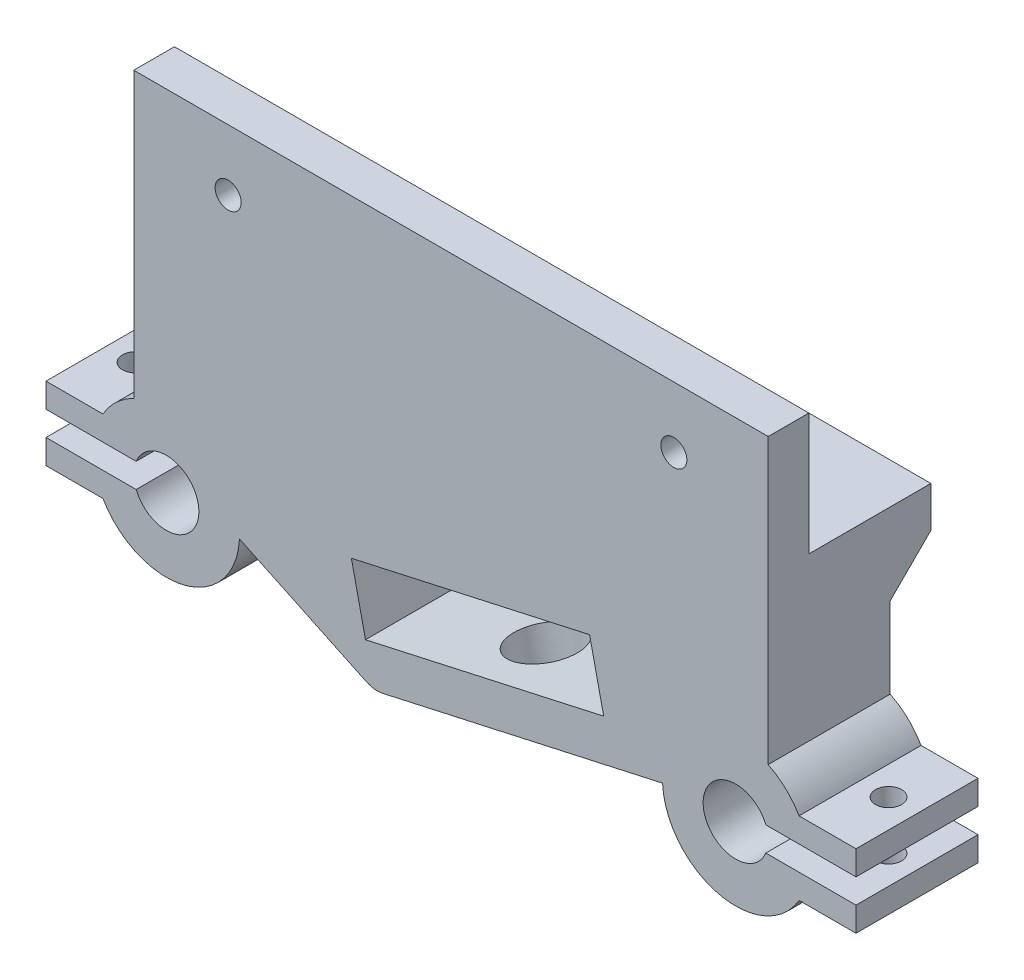
SolidWorks part; units mm, degrees
ref_plane "Front Plane" through (0, 0, 0) normal (0, 0, 1) x (1, 0, 0)
ref_plane "Top Plane" through (0, 0, 0) normal (0, 1, 0) x (1, 0, 0)
ref_plane "Right Plane" through (0, 0, 0) normal (1, 0, 0) x (0, 0, -1)
sketch "Sketch1" plane through (0, 0, 0) normal (0, 0, 1) x (1, 0, 0)
  line L0 (0, -1000) -> (0, 49000) construction
  line L1 (-39, 28) -> (39, 28)
  line L2 (39, 28) -> (39, 8.0623)
  line L3 (36.951, -8.786) -> (-23.8235, -22.2816)
  line L4 (-39, 28) -> (-39, 8.0623)
  line L6 (-34, 23) -> (34, 23)
  line L7 (34, 23) -> (34, 8.9443)
  line L9 (-13.0714, 45.025) -> (10825.8602, -48765.5982) construction
  line L10 (-1035, 0) -> (48965, 0) construction
  line L11 (-34, 23) -> (-34, 8.9443)
  line L12 (-22.3817, -16.8397) -> (-31.7139, -8.3786)
  line L13 (-23.8235, -22.2816) -> (-41.0451, -6.6675)
  line L14 (27.9966, -5.6526) -> (-22.3817, -16.8397)
  line L15 (-49.7942, 4.5) -> (-42.7942, 4.5)
  line L16 (-49.7942, 4.5) -> (-49.7942, 1.5)
  line L17 (-49.7942, 1.5) -> (-38.7081, 1.5)
  line L18 (42.7942, 4.5) -> (49.7942, 4.5)
  line L19 (-49.7942, -1.5) -> (-38.7081, -1.5)
  line L20 (-49.7942, -1.5) -> (-49.7942, -4.5)
  line L21 (-49.7942, -4.5) -> (-42.7942, -4.5)
  line L23 (38.7081, 1.5) -> (49.7942, 1.5)
  line L24 (49.7942, 4.5) -> (49.7942, 1.5)
  line L25 (38.7081, -1.5) -> (49.7942, -1.5)
  line L27 (42.7942, -4.5) -> (49.7942, -4.5)
  line L28 (49.7942, -1.5) -> (49.7942, -4.5)
  arc A0 (-38.7081, -1.5) -> (-38.7081, 1.5) centre (-35, 0) ccw
  arc A1 (38.7081, 1.5) -> (38.7081, -1.5) centre (35, 0) ccw
  arc A2 (34, 8.9443) -> (27.9966, -5.6526) centre (35, 0) ccw
  arc A3 (-39, 8.0623) -> (-42.7942, 4.5) centre (-35, 0) ccw
  arc A4 (-42.7942, -4.5) -> (-41.0451, -6.6675) centre (-35, 0) ccw
  arc A5 (-31.7139, -8.3786) -> (-34, 8.9443) centre (-35, 0) ccw
  arc A6 (36.951, -8.786) -> (42.7942, -4.5) centre (35, 0) ccw
  arc A8 (42.7942, 4.5) -> (39, 8.0623) centre (35, 0) ccw
  dimension "D1" = 8
  dimension "D2" = 70
  dimension "D4" = 18
  dimension "D5" = 19
  dimension "D14" = 9
  dimension "D3" = 102.52
  dimension "D6" = 5
  dimension "D7" = 5
  dimension "D8" = 3
  dimension "D9" = 3
  dimension "D10" = 22.5
  dimension "D11" = 5
  dimension "D12" = 5
  dimension "D13" = 3
  dimension "D15" = 7
  dimension "D16" = 3
  dimension "D17" = 7
  dimension "D18" = 5
  dimension "D19" = 90
  dimension "D20" = 3
sketch "Sketch2" plane through (0, 0, 0) normal (0, 0, 1) x (1, 0, 0)
  line L0 (-39, 28) -> (39, 28)
  line L1 (39, 28) -> (39, 8.0623)
  line L2 (-39, 28) -> (-39, 8.0623)
  line L3 (-42.7942, 4.5) -> (-49.7942, 4.5)
  line L4 (-49.7942, 4.5) -> (-49.7942, 1.5)
  line L5 (-49.7942, 1.5) -> (-38.7081, 1.5)
  line L6 (-38.7081, -1.5) -> (-49.7942, -1.5)
  line L7 (-49.7942, -1.5) -> (-49.7942, -4.5)
  line L8 (-49.7942, -4.5) -> (-42.7942, -4.5)
  line L10 (42.7942, 4.5) -> (49.7942, 4.5)
  line L11 (49.7942, 4.5) -> (49.7942, 1.5)
  line L12 (49.7942, 1.5) -> (38.7081, 1.5)
  line L13 (38.7081, -1.5) -> (49.7942, -1.5)
  line L14 (49.7942, -1.5) -> (49.7942, -4.5)
  line L15 (49.7942, -4.5) -> (42.7942, -4.5)
  line L17 (26.0093, -0.4085) -> (-9.4297, -8.2781)
  line L18 (-9.4297, -8.2781) -> (-26.0093, -0.4085)
  line L19 (27.9966, -5.6526) -> (-22.3817, -16.8397) construction
  line L20 (-43369.1498, 195289.1042) -> (54181.9386, -244009.6774) construction
  line L21 (-9.2108, 4.575) -> (14.2185, 9.7777) construction
  line L22 (-9.2108, 4.575) -> (-7.6933, -2.2586) construction
  line L23 (-7.6933, -2.2586) -> (15.736, 2.9441) construction
  line L24 (14.2185, 9.7777) -> (15.736, 2.9441) construction
  line L25 (-3.2618, 33.1405) -> (10835.7579, -48777.8793) construction
  line L27 (-10.5136, -3.397) -> (-12.2478, 4.4127)
  line L28 (-12.2478, 4.4127) -> (17.0388, 10.9161)
  line L29 (17.0388, 10.9161) -> (18.773, 3.1064)
  line L30 (18.773, 3.1064) -> (-10.5136, -3.397)
  line L32 (17.0388, 10.9161) -> (13.2451, 28) construction
  line L33 (-10.5136, -3.397) -> (-9.4297, -8.2781) construction
  arc A0 (-39, 8.0623) -> (-42.7942, 4.5) centre (-35, 0) ccw
  arc A1 (-39, 8.0623) -> (-42.7942, 4.5) centre (-35, 0) ccw construction
  arc A2 (39, 8.0623) -> (42.7942, 4.5) centre (35, 0) cw
  arc A3 (42.7942, 4.5) -> (39, 8.0623) centre (35, 0) ccw construction
  arc A4 (42.7942, -4.5) -> (26.0093, -0.4085) centre (35, 0) cw
  arc A5 (-42.7942, -4.5) -> (-26.0093, -0.4085) centre (-35, 0) ccw
  arc A6 (-38.7081, 1.5) -> (-38.7081, -1.5) centre (-35, 0) cw
  arc A7 (-38.7081, -1.5) -> (-38.7081, 1.5) centre (-35, 0) ccw construction
  arc A8 (38.7081, 1.5) -> (38.7081, -1.5) centre (35, 0) ccw
  arc A9 (38.7081, 1.5) -> (38.7081, -1.5) centre (35, 0) ccw construction
  dimension "D1" = 24
  dimension "D2" = 5
  dimension "D3" = 7
  dimension "D4" = 30
  dimension "D5" = 8
  dimension "D6" = 0.5
  dimension "D7" = 17.5
  dimension "D8" = 5
extrude "Boss-Extrude1" add sketch "Sketch2" against normal blind 15
sketch "Sketch3" plane through (0, 0, -15) normal (0, 0, -1) x (-1, 0, 0)
  line L0 (-34, 8.9443) -> (-34, 23)
  line L1 (-34, 23) -> (34, 23)
  line L2 (34, 23) -> (34, 8.9443)
  line L3 (-27.5547, 5.0565) -> (10.5136, -3.397)
  line L4 (10.5136, -3.397) -> (-18.773, 3.1064) construction
  line L5 (10.5136, -3.397) -> (12.2478, 4.4127)
  line L6 (12.2478, 4.4127) -> (27.156, 4.4127)
  arc A0 (-27.9966, -5.6526) -> (-34, 8.9443) centre (-35, 0) ccw construction
  arc A1 (34, 8.9443) -> (31.7139, -8.3786) centre (35, 0) ccw construction
  arc A2 (34, 8.9443) -> (27.156, 4.4127) centre (35, 0) ccw
  arc A3 (-34, 8.9443) -> (-27.5547, 5.0565) centre (-35, 0) cw
extrude "Cut-Extrude1" cut sketch "Sketch3" against normal blind 13
sketch "Sketch4" plane through (0, 0, -2) normal (0, 0, -1) x (-1, 0, 0)
  line L0 (-8.2528, 8.9651) -> (-6.5185, 16.7749)
  line L1 (12.2478, 4.4127) -> (-17.0388, 10.9161) construction
  line L2 (5.1961, 14.1735) -> (3.4619, 6.3638)
  line L3 (-6.5185, 16.7749) -> (5.1961, 14.1735)
  line L4 (-8.2528, 8.9651) -> (3.4619, 6.3638)
  line L5 (-3.8346, 1.1835) -> (10835.185, 48812.2033) construction
  line L6 (43369.1498, 195289.1042) -> (-54181.9386, -244009.6774) construction
  line L7 (-17.0388, 10.9161) -> (-18.773, 3.1064) construction
  line L8 (12.2478, 4.4127) -> (10.5136, -3.397) construction
  dimension "D1" = 12
  dimension "D2" = 8
extrude "Boss-Extrude2" add sketch "Sketch4" along normal blind 13
sketch "Sketch5" plane through (1.3087, -5.8935, 0) normal (0.2168, -0.9762, 0) x (0.9762, 0.2168, 0)
  line L0 (-1011, -7.5) -> (48989, -7.5) construction
  line L1 (-11, -15) -> (-11, 0) construction
  line L2 (4, -1015) -> (4, 48985) construction
  line L4 (10, -15) -> (10, -2) construction
  line L5 (-2, -15) -> (-2, -2) construction
  circle A0 centre (4, -7.5) radius 4
  point P7 (-11, -7.5)
  dimension "D1" = 8
extrude "Cut-Extrude2" cut sketch "Sketch5" against normal offset from surface (18 mm away) 5 up to face at (2.3955, 7.6644, -4.75) offset beyond the face yes
sketch "Sketch6" plane through (0, 28, 0) normal (0, 1, 0) x (1, 0, 0)
  line L0 (39, 15) -> (39, 0) construction
  line L1 (-39, 0) -> (39, 0)
  line L2 (-39, 0) -> (-39, 5)
  line L3 (-39, 5) -> (39, 5)
  line L4 (39, 0) -> (39, 5)
  dimension "D1" = 5
extrude "Boss-Extrude3" add sketch "Sketch6" along normal blind 15
sketch "Sketch7" plane through (0, 0, -15) normal (0, 0, -1) x (-1, 0, 0)
  line L0 (-39, 8.0623) -> (-39, 28) construction
  line L1 (39, 28) -> (-39, 28)
  line L2 (39, 28) -> (39, 23)
  line L3 (39, 23) -> (-39, 23)
  line L4 (-39, 28) -> (-39, 23)
  line L5 (34, 23) -> (-34, 23) construction
extrude "Boss-Extrude4" add sketch "Sketch7" along normal blind 5
sketch "Sketch8" plane through (0, 0, -5) normal (0, 0, -1) x (-1, 0, 0)
  line L0 (-961, 35.5) -> (49039, 35.5) construction
  line L1 (39, 43) -> (39, 28) construction
  line L2 (-39, 43) -> (-39, 28) construction
  circle A0 centre (27.4, 35.5) radius 1.6
  circle A1 centre (-27.4, 35.5) radius 1.6
  point P9 (39, 35.5)
  dimension "D1" = 3.2
  dimension "D2" = 11.6
  dimension "D3" = 11.6
extrude "Cut-Extrude3" cut sketch "Sketch8" against normal up to next
sketch "Sketch9" plane through (0, 28, 0) normal (0, 1, 0) x (1, 0, 0)
  line L0 (-1039, 12.5) -> (48961, 12.5) construction
  line L1 (-39, 20) -> (-39, 5) construction
  line L4 (39, 20) -> (39, 5) construction
  circle A0 centre (-27.4, 12.5) radius 1.6
  circle A1 centre (27.4, 12.5) radius 1.6
  point P5 (-39, 12.5)
  dimension "D1" = 3.2
  dimension "D2" = 11.6
  dimension "D3" = 11.6
extrude "Cut-Extrude4" cut sketch "Sketch9" against normal up to next
chamfer "Chamfer1" distance 5 angle 45 2 edges at (36.5, 23, -15) (-36.5, 23, -15)
fillet "Fillet1" radius 3 3 edges at (0.6612, 15.4742, -15) (-4.329, 10.2686, -15) (7.3857, 12.87, -15)
fillet "Fillet2" radius 3 1 edges at (-9.4297, -8.2781, -7.5)
sketch "Sketch10" plane through (0, -4.5, 0) normal (0, -1, 0) x (1, 0, 0)
  line L0 (46.2942, -1015) -> (46.2942, 48985) construction
  line L1 (42.7942, -15) -> (49.7942, -15) construction
  line L2 (-46.2942, -1015) -> (-46.2942, 48985) construction
  line L3 (-49.7942, -15) -> (-42.7942, -15) construction
  line L4 (-950.2058, -7.5) -> (49049.7942, -7.5) construction
  line L5 (49.7942, -15) -> (49.7942, 0) construction
  circle A0 centre (46.2942, -7.5) radius 1.6
  circle A1 centre (-46.2942, -7.5) radius 1.6
  point P9 (46.2942, -15)
  point P14 (-46.2942, -15)
  point P19 (49.7942, -7.5)
  dimension "D1" = 3.2
extrude "Cut-Extrude5" cut sketch "Sketch10" against normal through all
